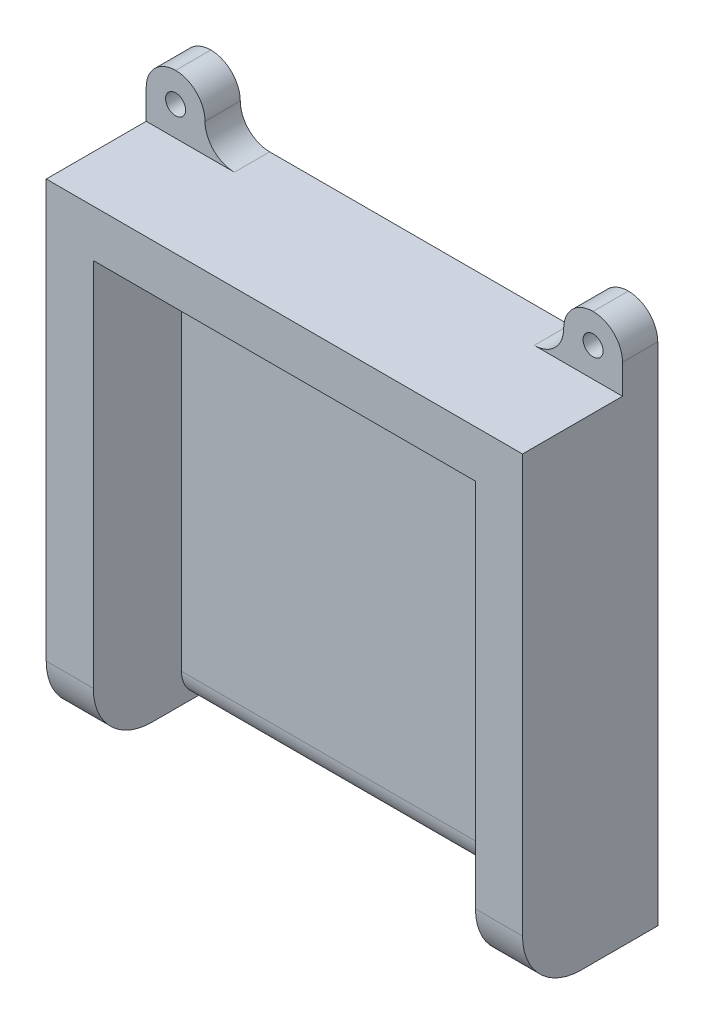
SolidWorks part; units mm, degrees
ref_plane "Plan de face" through (0, 0, 0) normal (0, 0, 1) x (1, 0, 0)
ref_plane "Plan de dessus" through (0, 0, 0) normal (0, 1, 0) x (1, 0, 0)
ref_plane "Plan de droite" through (0, 0, 0) normal (1, 0, 0) x (0, 0, -1)
sketch "Esquisse1" plane through (0, 0, 0) normal (0, 0, 1) x (1, 0, 0)
  line L1 (0, 0) -> (81, 0)
  line L2 (0, 0) -> (0, 81)
  line L3 (0, 81) -> (81, 81)
  line L4 (81, 0) -> (81, 81)
  dimension "D1" = 81
  dimension "D2" = 81
extrude "Boss.-Extru.1" add sketch "Esquisse1" along normal blind 8
sketch "Esquisse2" plane through (0, 0, 8) normal (0, 0, 1) x (1, 0, 0)
  line L1 (0, 81) -> (81, 81)
  line L3 (8, 73) -> (73, 73)
  line L4 (81, 81) -> (0, 81) construction
  line L6 (8, 73) -> (8, 0)
  line L8 (0, 81) -> (0, 0)
  line L9 (0, 0) -> (81, 0)
  line L10 (81, 0) -> (81, 81)
  line L11 (81, 81) -> (0, 81)
  line L12 (0, 81) -> (0, 0)
  line L13 (0, 0) -> (8, 0)
  line L14 (81, 0) -> (81, 81)
  line L16 (73, 73) -> (73, 0)
  line L17 (0, 0) -> (81, 0) construction
  line L19 (73, 0) -> (81, 0)
  dimension "D2" = 8
  dimension "D3" = 8
  dimension "D4" = 8
extrude "Boss.-Extru.2" add sketch "Esquisse2" along normal blind 15
fillet "Congé1" radius 10 2 edges at (77, 0, 23) (4, 0, 23)
fillet "Congé2" radius 5 1 edges at (40.5, 0, 8)
sketch "Esquisse3" plane through (0, 81, 0) normal (0, 1, 0) x (1, 0, 0)
  line L4 (40.5, 0) -> (40.5, -30.4724) construction
  line L5 (0, 0) -> (10, 0)
  line L6 (0, 0) -> (0, -6)
  line L7 (0, -6) -> (10, -6)
  line L8 (81, 0) -> (0, 0)
  line L9 (0, 0) -> (0, -23)
  line L10 (0, -23) -> (81, -23)
  line L11 (81, -23) -> (81, 0)
  line L12 (81, 0) -> (0, 0) construction
  line L13 (0, 0) -> (0, -23) construction
  line L14 (0, -23) -> (81, -23) construction
  line L15 (81, -23) -> (81, 0) construction
  line L16 (10, 0) -> (10, -6)
  line L17 (81, -6) -> (71, -6)
  line L18 (71, 0) -> (71, -6)
  line L19 (81, 0) -> (71, 0)
  line L20 (81, 0) -> (81, -6)
  dimension "D2" = 10
  dimension "D3" = 6
  dimension "D1" = 0
extrude "Boss.-Extru.3" add sketch "Esquisse3" along normal blind 10
fillet "Congé3" radius 5 6 edges at (0, 91, 3) (10, 91, 3) (10, 81, 3) (71, 81, 3) (71, 91, 3) (81, 91, 3)
sketch "Esquisse4" plane through (0, 0, 6) normal (0, 0, 1) x (1, 0, 0)
  line L0 (40.5, 81) -> (40.5, 90.0778) construction
  line L1 (81, 81) -> (0, 81) construction
  circle A0 centre (76, 86) radius 1
  circle A1 centre (5, 86) radius 1
  dimension "D1" = 2
hole_wizard "Dégagement M31" positions "Esquisse5" profile "Esquisse6" hole size "M3" standard "ISO" end condition through all
sketch "Esquisse5" plane through (0, 0, 6) normal (0, 0, 1) x (1, 0, 0)
  point P0 (76, 86)
  point P3 (5, 86)
sketch "Esquisse6" plane through (76, 86, 6) normal (1, 0, 0) x (0, -1, 0)
  line L0 (0, 0) -> (0, 6)
  line L1 (0, 6) -> (1.7, 6)
  line L2 (1.7, 6) -> (1.7, 0)
  line L5 (1.7, 0) -> (0, 0)
  line L11 (0, -6.35) -> (0, 107.95) construction
  dimension "Diamètre du perçage jusqu'au prochain" = 3.4
  dimension "Profondeur du perçage jusqu'au prochain" = 6
equation "\"epaiss_cadre\"= 8"
equation "\"D2@Esquisse1\"=\"epaiss_cadre\"*2+65"
equation "\"D1@Esquisse1\"=\"epaiss_cadre\"*2+65"
equation "\"D1@Boss.-Extru.1\"=\"epaiss_cadre\""
equation "\"D2@Esquisse2\"=\"epaiss_cadre\""
equation "\"D3@Esquisse2\"=\"epaiss_cadre\""
equation "\"D4@Esquisse2\"=\"epaiss_cadre\""
